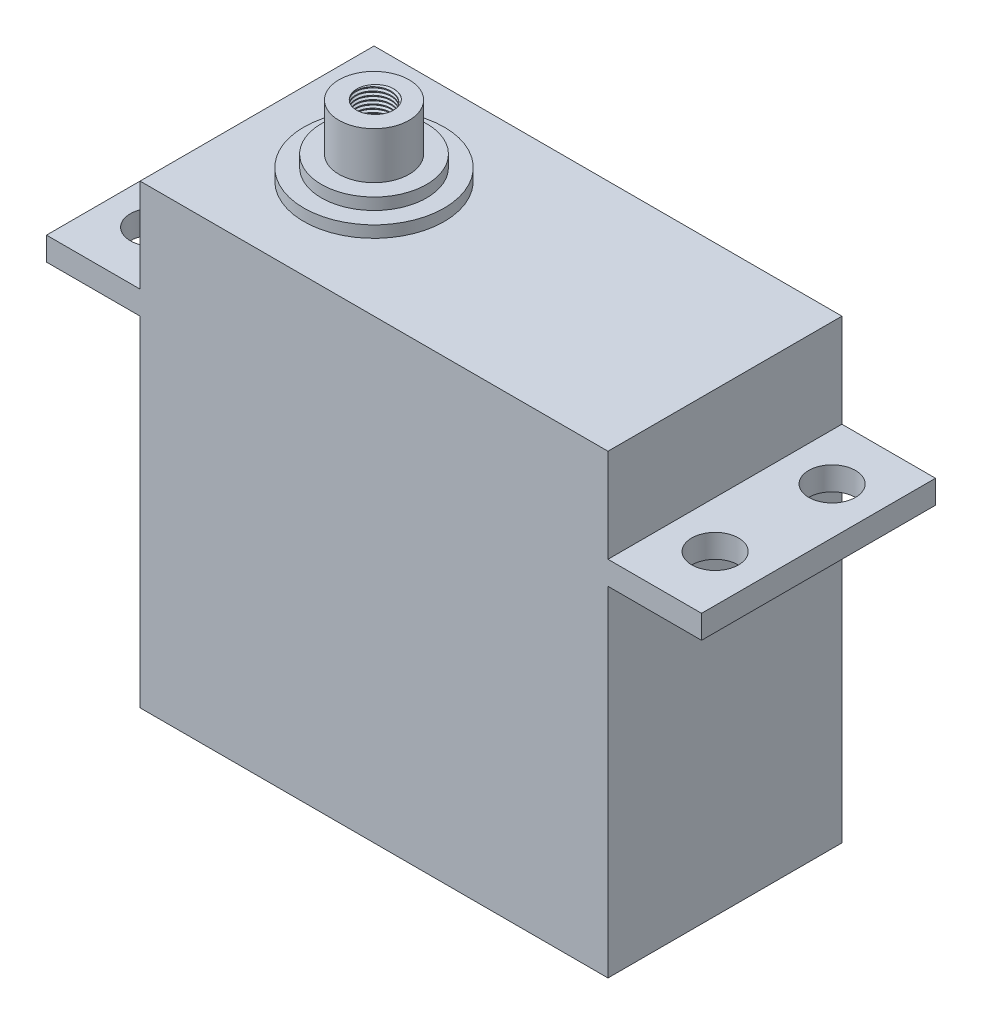
SolidWorks part; units mm, degrees
note: The reader was unsure of these and kept them because the rebuilt part matched: shared geometry of "草图5<4>", "草图5<5>", "草图5<6>", "草图5<7>", "草图5<8>", "草图5<9>".
ref_plane "前视基准面" through (0, 0, 0) normal (0, 0, 1) x (1, 0, 0)
ref_plane "上视基准面" through (0, 0, 0) normal (0, 1, 0) x (1, 0, 0)
ref_plane "右视基准面" through (0, 0, 0) normal (1, 0, 0) x (0, 0, -1)
other "Configuration Table"
sketch "草图1" plane through (0, 0, 0) normal (0, 0, 1) x (1, 0, 0)
  line L0 (-20, 12.316) -> (-20, 4.316)
  line L1 (-20, 2.316) -> (-20, -26.684)
  line L2 (-20, 12.316) -> (20, 12.316)
  line L4 (-20, -26.684) -> (20, -26.684)
  line L6 (28, 4.316) -> (28, 2.316)
  line L7 (-20, 4.316) -> (-28, 4.316)
  line L9 (-20, 2.316) -> (-28, 2.316)
  line L10 (-28, 4.316) -> (-28, 2.316)
  line L11 (20, 4.316) -> (28, 4.316)
  line L12 (20, 2.316) -> (28, 2.316)
  line L14 (20, 12.316) -> (20, 4.316)
  line L15 (20, 2.316) -> (20, -26.684)
  dimension "D1" = 40
  dimension "D2" = 39
  dimension "D3" = 8
  dimension "D4" = 2
  dimension "D5" = 8
extrude "凸台-拉伸2" add sketch "草图1" along normal blind 20
sketch "草图5" plane through (0, 4.316, 0) normal (0, 1, 0) x (1, 0, 0)
  line L2 (0, 0) -> (0, -29.2912) construction
  line L3 (-20, -20) -> (-20, 0) construction
  line L4 (-20, -10) -> (-10, -10)
  circle A0 centre (-24, -4.8398) radius 2
  circle A1 centre (-24, -14.8398) radius 2
  circle A2 centre (24, -14.8398) radius 2
  circle A3 centre (24, -4.8398) radius 2
  circle A4 centre (-10, -10) radius 6
  circle A5 centre (-10, -10) radius 4.5
  circle A6 centre (-10, -10) radius 3
  circle A7 centre (-10, -10) radius 1.5
extrude "凸台-拉伸4" add sketch "草图5" along normal blind 14 contours A6
extrude "凸台-拉伸5" add sketch "草图5<4>" along normal blind 9 contours A4
sketch "草图5<4>" plane through (0, 4.316, 0) normal (0, 1, 0) x (1, 0, 0) same geometry as "草图5"
extrude "凸台-拉伸6" add sketch "草图5<5>" along normal blind 10 contours A5
sketch "草图5<5>" plane through (0, 4.316, 0) normal (0, 1, 0) x (1, 0, 0) same geometry as "草图5"
extrude "切除-拉伸1" cut sketch "草图5<6>" against normal blind 10 contours A1
sketch "草图5<6>" plane through (0, 4.316, 0) normal (0, 1, 0) x (1, 0, 0) same geometry as "草图5"
extrude "切除-拉伸2" cut sketch "草图5<7>" against normal blind 10 contours A0
sketch "草图5<7>" plane through (0, 4.316, 0) normal (0, 1, 0) x (1, 0, 0) same geometry as "草图5"
extrude "切除-拉伸3" cut sketch "草图5<8>" against normal blind 10 contours A3
sketch "草图5<8>" plane through (0, 4.316, 0) normal (0, 1, 0) x (1, 0, 0) same geometry as "草图5"
extrude "切除-拉伸4" cut sketch "草图5<9>" against normal blind 10 contours A2
sketch "草图5<9>" plane through (0, 4.316, 0) normal (0, 1, 0) x (1, 0, 0) same geometry as "草图5"
sketch "草图6" plane through (0, 18.316, 0) normal (0, 1, 0) x (1, 0, 0)
  circle A0 centre (-10, -10) radius 1.5
extrude "切除-拉伸5" cut sketch "草图6" against normal blind 4 contours A0
thread "螺纹线1" pitch 0.3175 start angle 0, offset 0, length 4, pitch 0.3175, diameter 3
ref_plane "基准面1" through (-8.5, 14.316, 10) normal (0, 0, 1) x (1, 0, 0)
sketch "螺纹线轮廓1" plane through (-8.5, 14.316, 10) normal (0, 0, 1) x (1, 0, 0)
  line L0 (0, 0) -> (0, 0.3175) construction
  line L1 (0, 0) -> (0.1719, 0.0992)
  line L2 (0.1719, 0.0992) -> (0.1719, 0.1389)
  line L3 (0.1719, 0.1389) -> (0, 0.2381)
  line L4 (0.1719, 0.1191) -> (0, 0.1191) construction
  line L11 (0, 0) -> (0, 0.2381)
  point P2 (0, 0)
  dimension "Pitch" = 0.3175
  dimension "Profile_Angle" = 60
  dimension "Profile_Land" = 0.0397
  dimension "Profile_Height" = 0.1719
